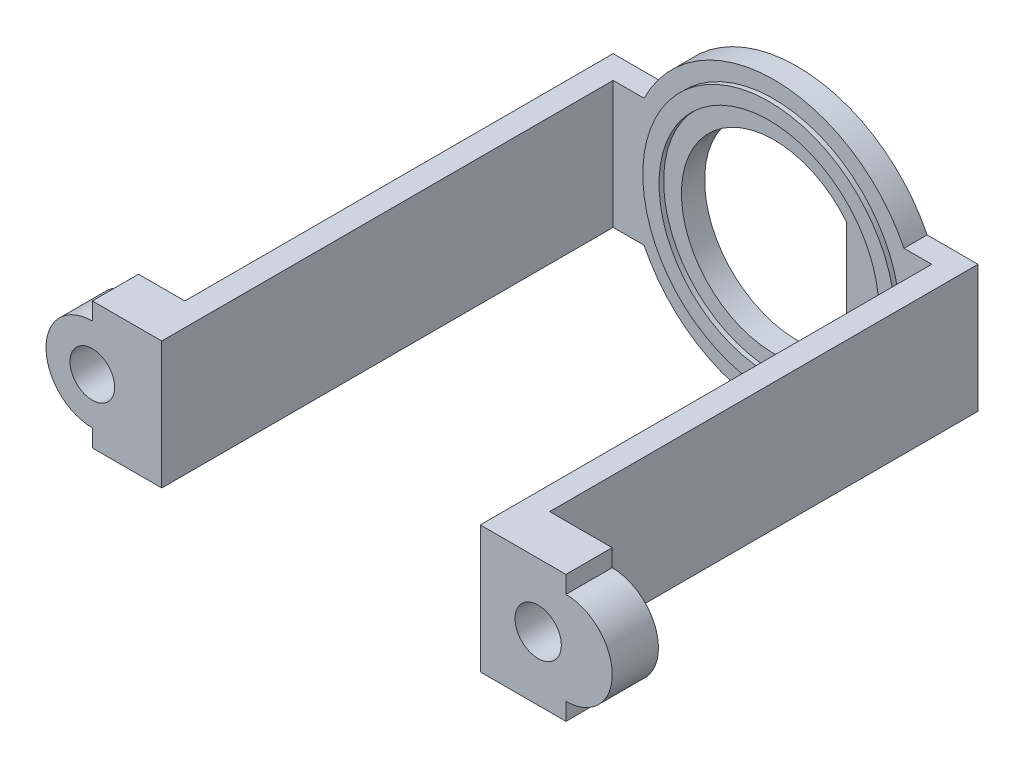
SolidWorks part; units mm, degrees
ref_plane "Front" through (0, 0, 0) normal (0, 0, 1) x (1, 0, 0)
ref_plane "Top" through (0, 0, 0) normal (0, 1, 0) x (1, 0, 0)
ref_plane "Right" through (0, 0, 0) normal (1, 0, 0) x (0, 0, -1)
sketch "Sketch1" plane through (0, 0, 0) normal (0, 0, 1) x (1, 0, 0)
  line L1 (0, 0) -> (20.0152, 0)
  line L2 (0, 0) -> (0, -6.985)
  line L3 (0, -6.985) -> (20.0152, -6.985)
  line L4 (20.0152, 0) -> (20.0152, -6.985)
  dimension "D1" = 20.0152
  dimension "D2" = 6.985
extrude "Extrude1" add sketch "Sketch1" along normal blind 1.27
sketch "Sketch2" plane through (0, 0, 0) normal (0, 0, -1) x (-1, 0, 0)
  circle A0 centre (-10.0965, -3.4925) radius 7.9375
  dimension "D1" = 15.875
  dimension "D2" = 3.4925
  dimension "D3" = 9.9187
extrude "Extrude2" add sketch "Sketch2" against normal blind 1.27
sketch "Sketch3" plane through (0, 0, 0) normal (0, 0, -1) x (-1, 0, 0)
  line L0 (-14.0621, -0.3175) -> (-14.0621, -6.6675)
  arc A0 (-14.0621, -0.3175) -> (-14.0621, -6.6675) centre (-10.0965, -3.4925) cw
  arc A1 (-2.9686, 0) -> (-17.2244, 0) centre (-10.0965, -3.4925) ccw construction
  arc A2 (-17.2244, -6.985) -> (-2.9686, -6.985) centre (-10.0965, -3.4925) ccw construction
  dimension "D1" = 5.08
  dimension "D2" = 6.35
extrude "Cut-Extrude1" cut sketch "Sketch3" against normal blind 2.54
sketch "Sketch4" plane through (0, 0, 1.27) normal (0, 0, 1) x (1, 0, 0)
  line L1 (0, 0) -> (1.27, 0)
  line L2 (0, 0) -> (0, -6.985)
  line L3 (0, -6.985) -> (1.27, -6.985)
  line L4 (1.27, 0) -> (1.27, -6.985)
  line L5 (20.0152, 0) -> (18.7452, 0)
  line L6 (20.0152, 0) -> (20.0152, -6.985)
  line L7 (20.0152, -6.985) -> (18.7452, -6.985)
  line L8 (18.7452, 0) -> (18.7452, -6.985)
  dimension "D1" = 1.27
  dimension "D2" = 1.27
extrude "Extrude4" add sketch "Sketch4" along normal blind 24.765
sketch "Sketch5" plane through (0, 0, 0) normal (-1, 0, 0) x (0, 0, 1)
  line L1 (26.035, 0) -> (23.4996, 0)
  line L2 (26.035, 0) -> (26.035, -6.985)
  line L3 (26.035, -6.985) -> (23.4996, -6.985)
  line L4 (23.4996, 0) -> (23.4996, -6.985)
extrude "Extrude5" add sketch "Sketch5" along normal blind 5.08
sketch "Sketch6" plane through (20.0152, 0, 0) normal (1, 0, 0) x (0, 0, -1)
  line L1 (-26.035, 0) -> (-23.4996, 0)
  line L2 (-26.035, 0) -> (-26.035, -6.985)
  line L3 (-26.035, -6.985) -> (-23.4996, -6.985)
  line L4 (-23.4996, 0) -> (-23.4996, -6.985)
extrude "Extrude6" add sketch "Sketch6" along normal blind 5.969
sketch "Sketch7" plane through (0, 0, 26.035) normal (0, 0, 1) x (1, 0, 0)
  line L2 (-5.08, -6.985) -> (-5.08, 0) construction
  line L3 (-5.08, -6.985) -> (1.27, -6.985) construction
  line L4 (-2.54, -0.9525) -> (-2.54, 0)
  line L5 (1.27, 0) -> (-5.08, 0) construction
  line L6 (-2.54, -6.0325) -> (-2.54, -6.985)
  arc A0 (-2.54, -6.0325) -> (-2.54, -0.9525) centre (-2.54, -3.4925) cw
  dimension "D2" = 2.54
  dimension "D1" = 3.4925
  dimension "D3" = 2.54
  dimension "D4" = 2.54
  dimension "D5" = 2.54
extrude "Cut-Extrude4" cut sketch "Sketch7" against normal through all and the other way through all flip side to cut
sketch "Sketch8" plane through (0, 0, 26.035) normal (0, 0, 1) x (1, 0, 0)
  circle A0 centre (-2.54, -3.4925) radius 1.2248
  arc A1 (-2.54, -0.9525) -> (-2.54, -6.0325) centre (-2.54, -3.4925) ccw construction
extrude "Cut-Extrude5" cut sketch "Sketch8" against normal blind 5.969
sketch "Sketch9" plane through (0, 0, 26.035) normal (0, 0, 1) x (1, 0, 0)
  line L0 (25.9842, 0) -> (25.9842, -6.985) construction
  line L1 (23.4442, -0.9525) -> (23.4442, 0)
  line L2 (25.9842, 0) -> (18.7452, 0) construction
  line L3 (23.4442, -6.0325) -> (23.4442, -6.985)
  line L4 (18.7452, -6.985) -> (25.9842, -6.985) construction
  arc A0 (23.4442, -0.9525) -> (23.4442, -6.0325) centre (23.4442, -3.4925) cw
  dimension "D1" = 2.54
  dimension "D2" = 2.54
  dimension "D3" = 2.54
  dimension "D4" = 2.54
  dimension "D5" = 3.4925
extrude "Cut-Extrude6" cut sketch "Sketch9" against normal through all and the other way through all
sketch "Sketch10" plane through (0, 0, 26.035) normal (0, 0, 1) x (1, 0, 0)
  line L0 (23.4442, -6.985) -> (20.0152, -6.985) construction
  line L1 (23.4442, 0) -> (18.7452, 0) construction
  line L3 (18.7452, 0) -> (18.7452, -6.985) construction
  circle A0 centre (21.9202, -3.4925) radius 1.27
  dimension "D3" = 2.54
  dimension "D1" = 3.4925
  dimension "D2" = 3.175
extrude "Cut-Extrude7" cut sketch "Sketch10" against normal blind 5.969
sketch "Sketch11" plane through (0, 0, 1.27) normal (0, 0, 1) x (1, 0, 0)
  circle A0 centre (10.0725, -3.3937) radius 6.9215
  circle A1 centre (10.0725, -3.3937) radius 6.0325
  dimension "D1" = 12.065
  dimension "D2" = 13.843
extrude "Extrude7" add sketch "Sketch11" along normal blind 0.254
